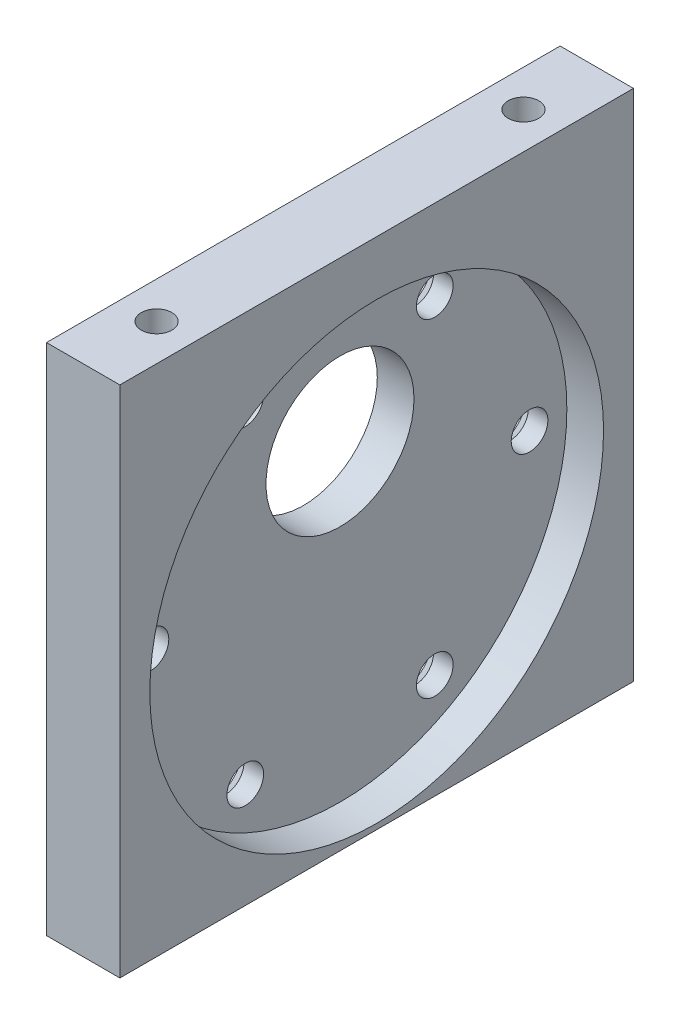
SolidWorks part; units mm, degrees
material "1060 Alloy"
ref_plane "Front Plane" through (0, 0, 0) normal (0, 0, 1) x (1, 0, 0)
ref_plane "Top Plane" through (0, 0, 0) normal (0, 1, 0) x (1, 0, 0)
ref_plane "Right Plane" through (0, 0, 0) normal (1, 0, 0) x (0, 0, -1)
sketch "Sketch1" plane through (0, 0, 0) normal (0, 1, 0) x (1, 0, 0)
  line L1 (0, 0) -> (6, 0)
  line L2 (0, 0) -> (0, 42)
  line L3 (0, 42) -> (6, 42)
  line L4 (6, 0) -> (6, 42)
  dimension "D1" = 42
  dimension "D2" = 6
extrude "Boss-Extrude1" add sketch "Sketch1" along normal blind 42
hole_wizard "Tap Drill for M3 Tap1" positions "Sketch3" profile "Sketch2" hole size "M3" standard "ISO"
sketch "Sketch3" plane through (0, 42, 0) normal (0, 1, 0) x (-1, 0, 0)
  line L0 (0, 0) -> (-6, 0) construction
  line L1 (-6, 0) -> (-6, -42) construction
  line L2 (-6, -42) -> (0, -42) construction
  point P0 (-3, -6)
  point P1 (-3, -36)
  point P6 (-3, -42)
  dimension "D1" = 6
  dimension "D2" = 3
  dimension "D3" = 6
sketch "Sketch2" plane through (3, 42, -6) normal (1, 0, 0) x (0, 0, 1)
  line L0 (0, 0) -> (0, 10.7511)
  line L1 (0, 10.7511) -> (1.25, 10)
  line L2 (1.25, 10) -> (1.25, 0)
  line L5 (1.25, 0) -> (0, 0)
  line L10 (0, 10.7511) -> (-1.25, 10) construction
  line L11 (0, -6.35) -> (0, 107.95) construction
  dimension "Hole Dia." = 2.5
  dimension "Hole Depth" = 10
  dimension "Drill Angle" = 118
hole_wizard "Tap Drill for M3 Tap2" positions "Sketch5" profile "Sketch4" hole size "M3" standard "ISO"
sketch "Sketch5" plane through (0, 0, 0) normal (0, -1, 0) x (1, 0, 0)
  line L0 (6, 0) -> (6, -42) construction
  line L1 (0, 0) -> (6, 0) construction
  line L2 (6, -42) -> (0, -42) construction
  point P0 (3, -6)
  point P1 (3, -36)
  dimension "D1" = 3
  dimension "D2" = 6
  dimension "D3" = 6
sketch "Sketch4" plane through (3, 0, -6) normal (1, 0, 0) x (0, 0, -1)
  line L0 (0, 0) -> (0, 6.7511)
  line L1 (0, 6.7511) -> (1.25, 6)
  line L2 (1.25, 6) -> (1.25, 0)
  line L5 (1.25, 0) -> (0, 0)
  line L10 (0, 6.7511) -> (-1.25, 6) construction
  line L11 (0, -6.35) -> (0, 107.95) construction
  dimension "Hole Dia." = 2.5
  dimension "Hole Depth" = 6
  dimension "Drill Angle" = 118
sketch "Sketch6" plane through (6, 0, 0) normal (1, 0, 0) x (0, 0, -1)
  line L0 (0, 42) -> (0, 0) construction
  line L1 (0, 0) -> (42, 0) construction
  circle A0 centre (21, 19) radius 18.55
  dimension "D2" = 37.1
  dimension "D1" = 21
  dimension "D3" = 19
extrude "Cut-Extrude1" cut sketch "Sketch6" against normal blind 3
sketch "Sketch7" plane through (3, 0, 0) normal (1, 0, 0) x (0, 0, -1)
  line L1 (2.45, 19) -> (21, 19) construction
  circle A0 centre (21, 26) radius 6.05
  circle A1 centre (21, 19) radius 18.55 construction
  circle A3 centre (5.5, 19) radius 1.5
  circle A4 centre (21, 19) radius 18.55 construction
  dimension "D1" = 12.1
  dimension "D4" = 3
  dimension "D2" = 21
  dimension "D3" = 7
  dimension "D5" = 15.5
extrude "Cut-Extrude2" cut sketch "Sketch7" against normal up to next
pattern_circular "CirPattern1" count 6 over 360 about axis through (6, 19, -21) along (1, 0, 0) of face at (3, 19, -7)
chamfer "Chamfer1" distance 1.4 angle 45 6 edges at (0, 19, -35) (0, 6.8756, -28) (0, 6.8756, -14) (0, 19, -7) (0, 31.1244, -14) (0, 31.1244, -28)
